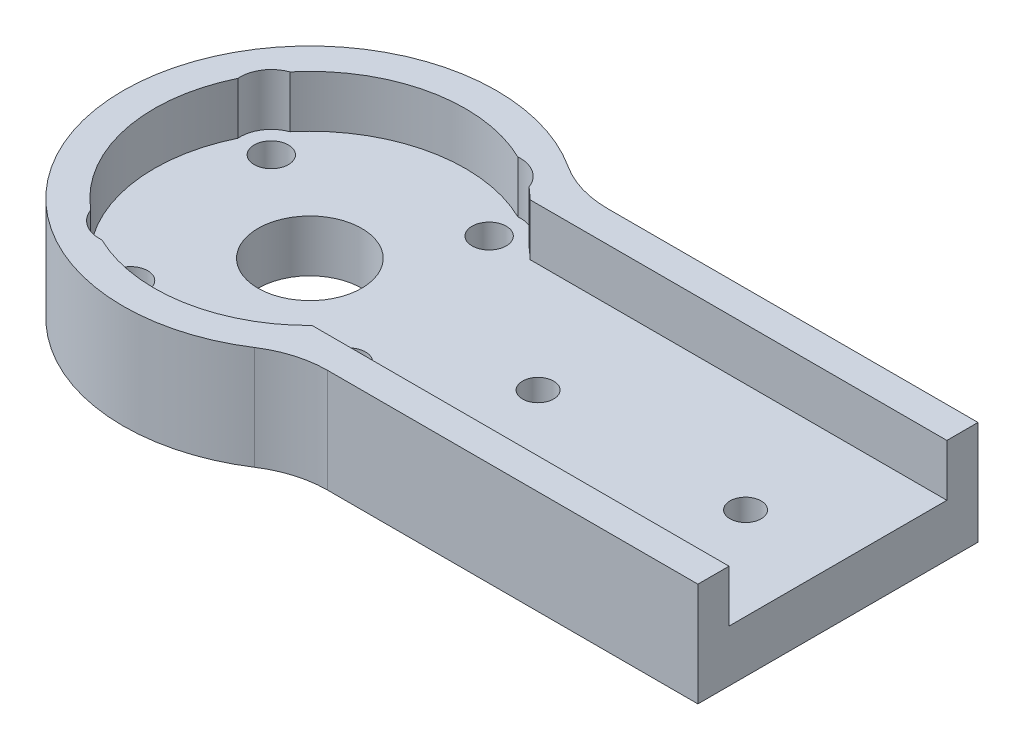
SolidWorks part; units mm, degrees
material "ABS"
ref_plane "Front Plane" through (0, 0, 0) normal (0, 0, 1) x (1, 0, 0)
ref_plane "Top Plane" through (0, 0, 0) normal (0, 1, 0) x (1, 0, 0)
ref_plane "Right Plane" through (0, 0, 0) normal (1, 0, 0) x (0, 0, -1)
sketch "Sketch1" plane through (0, 0, 0) normal (0, 1, 0) x (1, 0, 0)
  line L1 (11.9059, 13.5) -> (50.9059, 13.5)
  line L3 (11.9059, -13.5) -> (50.9059, -13.5)
  line L4 (50.9059, 13.5) -> (50.9059, -13.5)
  arc A0 (11.9059, 13.5) -> (11.9059, -13.5) centre (0, 0) ccw
  dimension "D1" = 36
  dimension "D2" = 39
extrude "Boss-Extrude1" add sketch "Sketch1" along normal blind 5
sketch "Sketch2" plane through (0, 5, 0) normal (0, 1, 0) x (1, 0, 0)
  circle A0 centre (0, 0) radius 5
  dimension "D1" = 10
extrude "Cut-Extrude1" cut sketch "Sketch2" against normal blind 5
sketch "Sketch3" plane through (0, 5, 0) normal (0, 1, 0) x (1, 0, 0)
  line L0 (11.9059, -13.5) -> (50.9059, -13.5) construction
  circle A0 centre (6.7823, 10.5) radius 1.65
  circle A1 centre (0, 0) radius 5 construction
  circle A2 centre (10.5, -6.7823) radius 1.65
  circle A3 centre (-6.7823, -10.5) radius 1.65
  circle A4 centre (-10.5, 6.7823) radius 1.65
  point P15 (0, 0)
  dimension "D1" = 3.3
  dimension "D2" = 12.5
  dimension "D3" = 24
  dimension "D4" = 4
extrude "Cut-Extrude2" cut sketch "Sketch3" against normal up to vertex (5 mm away) up to point (0, 0, 0)
sketch "Sketch4" plane through (0, 5, 0) normal (0, 1, 0) x (1, 0, 0)
  circle A0 centre (22, 0) radius 1.5
  circle A1 centre (42, 0) radius 1.5
  circle A2 centre (0, 0) radius 5 construction
  dimension "D1" = 3
  dimension "D2" = 3
  dimension "D3" = 22
  dimension "D4" = 20
extrude "Cut-Extrude3" cut sketch "Sketch4" against normal blind 5
sketch "Sketch5" plane through (0, 5, 0) normal (0, 1, 0) x (1, 0, 0)
  line L1 (50.9059, 13.5) -> (11.9059, 13.5)
  line L2 (50.9059, 13.5) -> (50.9059, 10.5)
  line L3 (50.9059, 10.5) -> (10.7121, 10.5)
  line L5 (50.9059, -13.5) -> (11.9059, -13.5)
  line L6 (50.9059, -13.5) -> (50.9059, -10.5)
  line L7 (50.9059, -10.5) -> (10.7121, -10.5)
  arc A0 (11.9059, 13.5) -> (11.9059, -13.5) centre (0, 0) ccw
  arc A1 (10.7121, 10.5) -> (10.7121, -10.5) centre (0, 0) ccw
  arc A2 (11.9059, 13.5) -> (11.9059, -13.5) centre (0, 0) ccw construction
  dimension "D1" = 3
  dimension "D3" = 3
  dimension "D4" = 0
  dimension "D2" = 3
extrude "Boss-Extrude2" add sketch "Sketch5" along normal blind 5
sketch "Sketch6" plane through (0, 5, 0) normal (0, 1, 0) x (1, 0, 0)
  circle A0 centre (-10.5, 6.7823) radius 3
  circle A1 centre (6.7823, 10.5) radius 3
  circle A2 centre (-6.7823, -10.5) radius 3
  dimension "D1" = 6
  dimension "D2" = 6
  dimension "D3" = 6
extrude "Cut-Extrude4" cut sketch "Sketch6" along normal blind 5
fillet "Fillet1" radius 10 2 edges at (11.9059, 5, -13.5) (11.9059, 5, 13.5)
